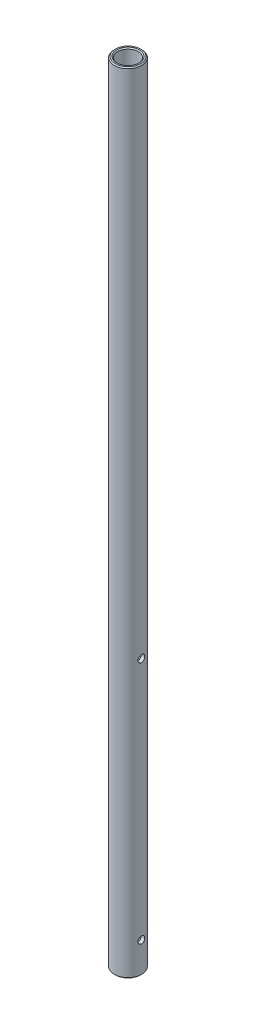
SolidWorks part; units mm, degrees
material "AISI 304"
ref_plane "Спереди" through (0, 0, 0) normal (0, 0, 1) x (1, 0, 0)
ref_plane "Сверху" through (0, 0, 0) normal (0, 1, 0) x (1, 0, 0)
ref_plane "Справа" through (0, 0, 0) normal (1, 0, 0) x (0, 0, -1)
other "Configuration Table"
sketch "Эскиз1" plane through (0, 0, 0) normal (0, 1, 0) x (1, 0, 0)
  circle A0 centre (0, 0) radius 4
  circle A1 centre (0, 0) radius 3
  dimension "D1" = 8
  dimension "D2" = 6
extrude "Бобышка-Вытянуть1" add sketch "Эскиз1" along normal blind 230
chamfer "Фаска1" distance 0.3 angle 45 4 edges at (0, 230, 3) (0, 0, 3) (0, 0, 4) (0, 230, 4)
sketch "Эскиз2" plane through (0, 0, 0) normal (1, 0, 0) x (0, 0, -1)
  circle A0 centre (0, 9) radius 1 construction
  circle A1 centre (0, 9) radius 1
extrude "Вырез-Вытянуть1" cut sketch "Эскиз2" against normal through all both and the other way through all
sketch "Эскиз3" plane through (0, 0, 0) normal (1, 0, 0) x (0, 0, -1)
  circle A0 centre (0, 80) radius 1.25 construction
  circle A3 centre (0, 9) radius 1 construction
  circle A4 centre (0, 9) radius 1 construction
  circle A5 centre (0, 80) radius 1.25 construction
  circle A6 centre (0, 80) radius 1
  dimension "D1" = 2
extrude "Вырез-Вытянуть2" cut sketch "Эскиз3" against normal through all both and the other way through all
